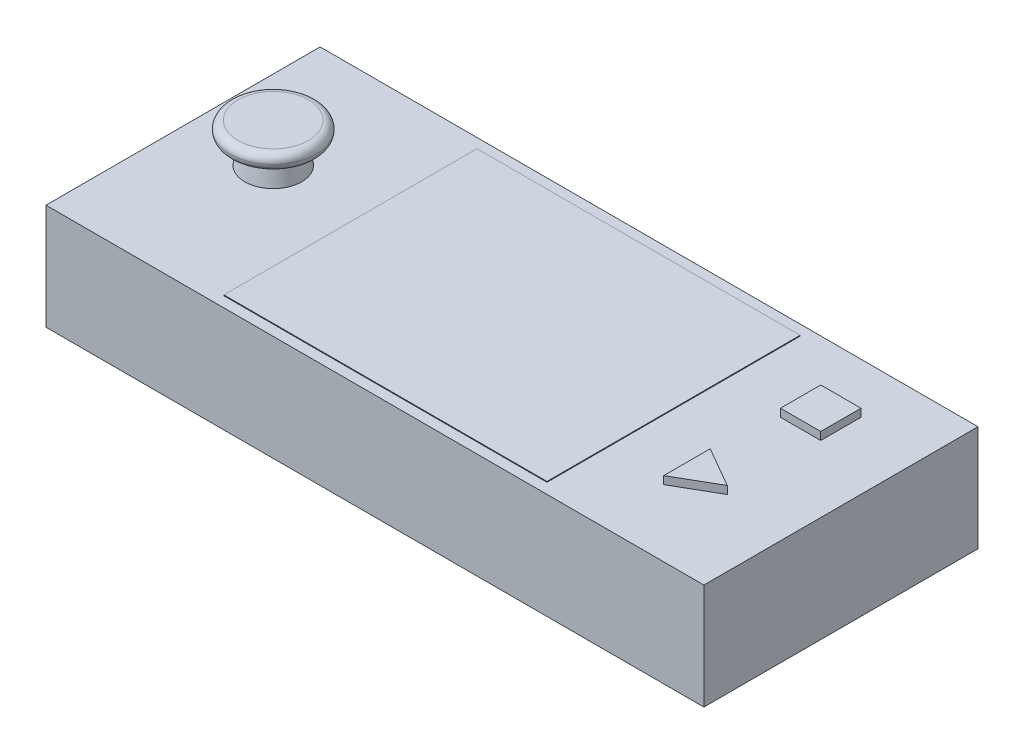
SolidWorks part; units mm, degrees
ref_plane "前视基准面" through (0, 0, 0) normal (0, 0, 1) x (1, 0, 0)
ref_plane "上视基准面" through (0, 0, 0) normal (0, 1, 0) x (1, 0, 0)
ref_plane "右视基准面" through (0, 0, 0) normal (1, 0, 0) x (0, 0, -1)
other "Configuration Table"
sketch "草图1" plane through (0, 0, 0) normal (0, 1, 0) x (1, 0, 0)
  line L1 (-42, -17.5) -> (42, -17.5)
  line L2 (-42, -17.5) -> (-42, 17.5)
  line L3 (-42, 17.5) -> (42, 17.5)
  line L4 (42, -17.5) -> (42, 17.5)
  line L5 (-42, -17.5) -> (42, 17.5) construction
  line L6 (-42, 17.5) -> (42, -17.5) construction
  point P0 (0, 0)
  dimension "D1" = 84
  dimension "D2" = 35
extrude "凸台-拉伸1" add sketch "草图1" along normal blind 13.5
sketch "草图2" plane through (0, 13.5, 0) normal (0, 1, 0) x (1, 0, 0)
  line L1 (28.3415, 11.0795) -> (33.4833, 11.0795)
  line L2 (28.3415, 11.0795) -> (28.3415, 5.9376)
  line L3 (28.3415, 5.9376) -> (33.4833, 5.9376)
  line L4 (33.4833, 11.0795) -> (33.4833, 5.9376)
  line L5 (28.3415, 11.0795) -> (33.4833, 5.9376) construction
  line L6 (28.3415, 5.9376) -> (33.4833, 11.0795) construction
  line L7 (33.4833, -5.9988) -> (28.3415, -3.0302)
  line L8 (28.3415, -3.0302) -> (28.3415, -8.9675)
  line L9 (28.3415, -8.9675) -> (33.4833, -5.9988)
  line L10 (-20.6287, -16.1602) -> (20.6287, -16.1602)
  line L11 (-20.6287, -16.1602) -> (-20.6287, 16.1602)
  line L12 (-20.6287, 16.1602) -> (20.6287, 16.1602)
  line L13 (20.6287, -16.1602) -> (20.6287, 16.1602)
  line L14 (-20.6287, -16.1602) -> (20.6287, 16.1602) construction
  line L15 (-20.6287, 16.1602) -> (20.6287, -16.1602) construction
  circle A0 centre (-31.8918, 1.4079) radius 3.6369
  circle A1 centre (30.0554, -5.9988) radius 1.714 construction
  point P2 (30.9124, 8.5086)
  point P20 (0, 0)
extrude "凸台-拉伸2" add sketch "草图2" along normal blind 3 draft 10 contours A0 region at (-31.8918, 13.5, -1.4079)
extrude "凸台-拉伸3" add sketch "草图2<3>" along normal blind 1 contours L4 L1 L2 L3 | L8 L9 L7 region at (30.9124, 13.5, -8.5086) region at (30.0554, 13.5, 5.9988)
sketch "草图2<3>" plane through (0, 13.5, 0) normal (0, 1, 0) x (1, 0, 0) same geometry as "草图2"
extrude "凸台-拉伸4" add sketch "草图2<4>" along normal blind 0.1 contours L10 L13 L12 L11 region at (0, 13.5, 0)
sketch "草图2<4>" plane through (0, 13.5, 0) normal (0, 1, 0) x (1, 0, 0) same geometry as "草图2"
sketch "草图4" plane through (0, 16.5, 0) normal (0, 1, 0) x (1, 0, 0)
  circle A0 centre (-31.8918, 1.4079) radius 5.5
  circle A1 centre (-31.8918, 1.4079) radius 3.1079 construction
  dimension "D1" = 11
extrude "凸台-拉伸5" add sketch "草图4" along normal blind 2
fillet "圆角1" radius 1 2 edges at (-31.8918, 16.5, 4.0921) (-31.8918, 18.5, 4.0921)
sketch "草图5" plane through (0, 0, 0) normal (0, -1, 0) x (1, 0, 0)
  line L0 (-42, 0) -> (42, 0) construction
  line L1 (16.5, 10) -> (25.5, 10)
  line L2 (16.5, 10) -> (16.5, -10)
  line L3 (16.5, -10) -> (25.5, -10)
  line L4 (25.5, 10) -> (25.5, -10)
  line L5 (16.5, 10) -> (25.5, -10) construction
  line L6 (16.5, -10) -> (25.5, 10) construction
  line L7 (-42, -17.5) -> (-42, 17.5) construction
  line L8 (42, 17.5) -> (42, -17.5) construction
  circle A0 centre (-38, 8) radius 2
  circle A1 centre (-38, -8) radius 2
  circle A2 centre (10, 8) radius 2
  circle A3 centre (10, -8) radius 2
  point P8 (21, 0)
  dimension "D2" = 4
  dimension "D3" = 4
  dimension "D4" = 4
  dimension "D5" = 16
  dimension "D6" = 48
  dimension "D1" = 4
  dimension "D7" = 20
  dimension "D8" = 9
  dimension "D9" = 16.5
extrude "切除-拉伸1" cut sketch "草图5" against normal blind 6
equation "\"D2@草图5\"=\"D1@草图5\""
equation "\"D3@草图5\"=\"D1@草图5\""
equation "\"D4@草图5\"=\"D1@草图5\""
